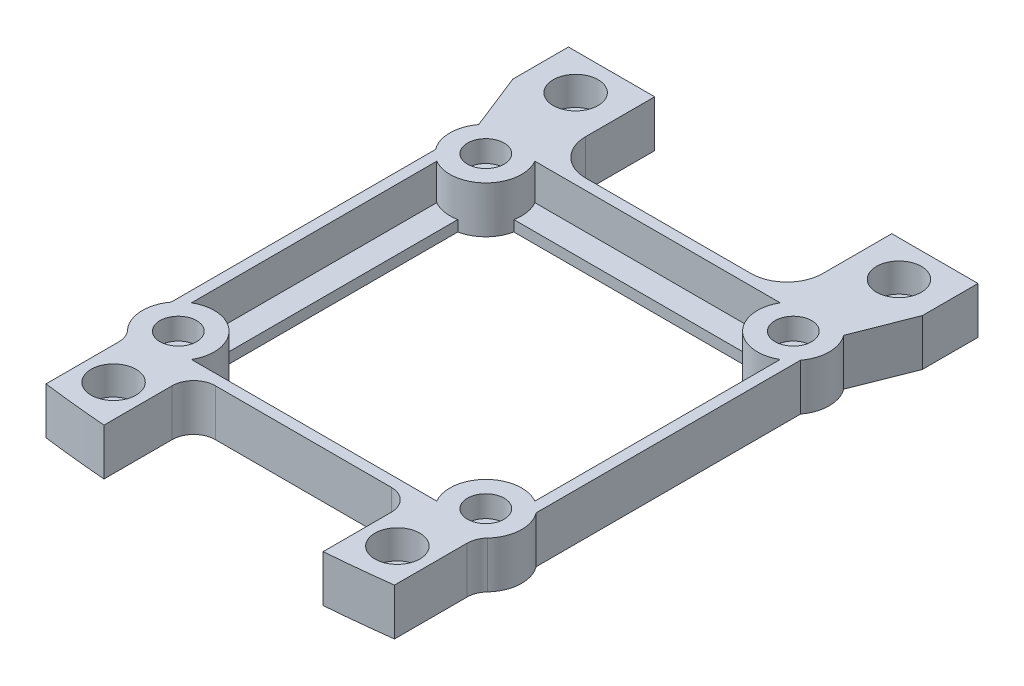
SolidWorks part; units mm, degrees
ref_plane "Front Plane" through (0, 0, 0) normal (0, 0, 1) x (1, 0, 0)
ref_plane "Top Plane" through (0, 0, 0) normal (0, 1, 0) x (1, 0, 0)
ref_plane "Right Plane" through (0, 0, 0) normal (1, 0, 0) x (0, 0, -1)
sketch "Sketch1" plane through (0, 0, 0) normal (0, 1, 0) x (1, 0, 0)
  line L0 (20.4, 20.4) -> (-20.4, 20.4)
  line L1 (21.4, -21.4) -> (-21.4, -21.4) construction
  line L2 (21.4, -21.4) -> (21.4, 21.4) construction
  line L3 (21.4, 21.4) -> (-21.4, 21.4) construction
  line L4 (-21.4, -21.4) -> (-21.4, 21.4) construction
  line L5 (21.4, -21.4) -> (-21.4, 21.4) construction
  line L6 (21.4, 21.4) -> (-21.4, -21.4) construction
  line L7 (-20.4, -20.4) -> (-20.4, 20.4)
  line L8 (20.4, -20.4) -> (-20.4, -20.4)
  line L9 (20.4, -20.4) -> (20.4, 20.4)
  line L10 (25.4, 25.4) -> (-25.4, 25.4)
  line L11 (-25.4, -25.4) -> (-25.4, 25.4)
  line L12 (25.4, -25.4) -> (-25.4, -25.4)
  line L13 (25.4, -25.4) -> (25.4, 25.4)
  circle A0 centre (-21.4, 21.4) radius 1.375
  circle A1 centre (21.4, 21.4) radius 1.375
  circle A2 centre (21.4, -21.4) radius 1.375
  circle A3 centre (-21.4, -21.4) radius 1.375
  point P0 (0, 0)
  dimension "D2" = 2.75
  dimension "D1" = 42.8
  dimension "D3" = 1
  dimension "D4" = 4
extrude "Boss-Extrude1" add sketch "Sketch1" along normal blind 1.5
sketch "Sketch2" plane through (0, 1.5, 0) normal (0, 1, 0) x (1, 0, 0)
  line L0 (23.9, 23.9) -> (-23.9, 23.9)
  line L1 (-23.9, 23.9) -> (-23.9, -23.9)
  line L2 (-23.9, -23.9) -> (23.9, -23.9)
  line L3 (23.9, -23.9) -> (23.9, 23.9)
  line L4 (25.4, -25.4) -> (25.4, 25.4)
  line L5 (25.4, 25.4) -> (-25.4, 25.4)
  line L6 (-25.4, 25.4) -> (-25.4, -25.4)
  line L7 (-25.4, -25.4) -> (25.4, -25.4)
  line L8 (25.4, -25.4) -> (25.4, 25.4)
  line L9 (25.4, 25.4) -> (-25.4, 25.4)
  line L10 (-25.4, 25.4) -> (-25.4, -25.4)
  line L11 (-25.4, -25.4) -> (25.4, -25.4)
  dimension "D1" = 0
  dimension "D2" = 1.5
extrude "Boss-Extrude2" add sketch "Sketch2" along normal blind 5
fillet "Fillet2" radius 3 8 edges at (23.9, 4, -23.9) (25.4, 3.25, -25.4) (23.9, 4, 23.9) (25.4, 3.25, 25.4) (-23.9, 4, 23.9) (-25.4, 3.25, 25.4) (-25.4, 3.25, -25.4) (-23.9, 4, -23.9)
sketch "Sketch5" plane through (0, 6.5, 0) normal (0, 1, 0) x (1, 0, 0)
  circle A0 centre (-21.4, 21.4) radius 5
  circle A1 centre (21.4, 21.4) radius 5
  circle A2 centre (21.4, -21.4) radius 5
  circle A3 centre (-21.4, -21.4) radius 5
  circle A4 centre (21.4, -21.4) radius 1.375 construction
  circle A5 centre (-21.4, -21.4) radius 1.375 construction
  circle A6 centre (21.4, 21.4) radius 1.375 construction
  circle A7 centre (-21.4, 21.4) radius 1.375 construction
  circle A8 centre (21.4, -21.4) radius 1.375
  circle A9 centre (-21.4, -21.4) radius 1.375
  circle A10 centre (21.4, 21.4) radius 1.375
  circle A11 centre (-21.4, 21.4) radius 1.375
  dimension "D1" = 10
extrude "Boss-Extrude3" add sketch "Sketch5" against normal up to surface (6.5 mm away) up to face at (-21.4, 0, 22.775)
sketch "Sketch6" plane through (0, 6.5, 0) normal (0, 1, 0) x (1, 0, 0)
  circle A0 centre (-21.4, 21.4) radius 2.55
  circle A1 centre (21.4, 21.4) radius 2.55
  circle A2 centre (-21.4, -21.4) radius 2.55
  circle A3 centre (21.4, -21.4) radius 2.55
  dimension "D1" = 5.1
extrude "Cut-Extrude1" cut sketch "Sketch6" against normal blind 3
sketch "Sketch7" plane through (0, 6.5, 0) normal (0, 1, 0) x (1, 0, 0)
  line L0 (16.5, 25.4) -> (16.5, 40)
  line L1 (18.4, 25.4) -> (-18.4, 25.4) construction
  line L2 (16.5, 40) -> (28.5, 40)
  line L5 (18.4, 25.4) -> (16.5, 25.4)
  line L7 (28.5, 40) -> (28.5, 32.25)
  line L8 (28.5, 32.25) -> (25.4, 24.4)
  line L9 (25.4, -18.4) -> (25.4, 18.4) construction
  arc A0 (25.4, 18.4) -> (18.4, 25.4) centre (21.4, 21.4) ccw construction
  arc A1 (25.4, 24.4) -> (18.4, 25.4) centre (21.4, 21.4) ccw
  circle A2 centre (22.5, 35) radius 1.55
  point P7 (22.5, 40)
  dimension "D5" = 5
  dimension "D6" = 3.1
  dimension "D1" = 40
  dimension "D2" = 16.5
  dimension "D3" = 12
  dimension "D4" = 7.75
extrude "Boss-Extrude4" add sketch "Sketch7" against normal up to surface (6.5 mm away) up to face at (0, 0, 0)
sketch "Sketch8" plane through (0, 6.5, 0) normal (0, 1, 0) x (1, 0, 0)
  circle A0 centre (22.5, 35) radius 3.125
  dimension "D1" = 6.25
extrude "Cut-Extrude2" cut sketch "Sketch8" against normal blind 4
mirror "Mirror1" about plane through (0, 0, 0) normal (1, 0, 0) of "Cut-Extrude2", "Boss-Extrude4"
fillet "Fillet3" radius 5 2 edges at (16.5, 3.25, -25.4) (-16.5, 3.25, -25.4)
sketch "Sketch9" plane through (0, 6.5, 0) normal (0, 1, 0) x (1, 0, 0)
  line L0 (-24.25, -25.5082) -> (-24.25, -36.9624)
  line L1 (-15.25, -25.4) -> (-15.25, -37.8934)
  line L2 (-18.4, -25.4) -> (18.4, -25.4) construction
  line L3 (-18.4, -25.4) -> (-15.25, -25.4)
  arc A0 (-25.4, -18.4) -> (-18.4, -25.4) centre (-21.4, -21.4) ccw construction
  arc A3 (-24.25, -25.5082) -> (-18.4, -25.4) centre (-21.4, -21.4) ccw
  arc A5 (-24.25, -36.9624) -> (-15.25, -37.8934) centre (0, 153.5) ccw
  arc A7 (-76.8129, -22.4653) -> (-4.75, -38.4412) centre (0, 153.5) ccw construction
  dimension "D1" = 9
  dimension "D2" = 15.25
extrude "Boss-Extrude5" add sketch "Sketch9" against normal up to surface (6.5 mm away) up to face at (0, 0, -18.1088)
sketch "Sketch10" plane through (0, 6.5, 0) normal (0, 1, 0) x (1, 0, 0)
  line L0 (-24.25, -32.06) -> (-15.25, -32.06) construction
  line L1 (-24.25, -25.5082) -> (-24.25, -36.9624) construction
  line L2 (-15.25, -37.8934) -> (-15.25, -25.4) construction
  line L3 (-15.25, -25.4) -> (18.4, -25.4) construction
  circle A0 centre (-19.75, -32.06) radius 3.125
  circle A2 centre (22.5, 35) radius 3.125 construction
  point P9 (-19.75, -32.06)
  dimension "D1" = 6.66
extrude "Cut-Extrude3" cut sketch "Sketch10" against normal blind 4
sketch "Sketch11" plane through (0, 2.5, 0) normal (0, 1, 0) x (1, 0, 0)
  circle A0 centre (-19.75, -32.06) radius 1.55
  dimension "D1" = 3.1
extrude "Cut-Extrude4" cut sketch "Sketch11" against normal through all
mirror "Mirror2" about plane through (0, 0, 0) normal (1, 0, 0) of "Cut-Extrude4", "Cut-Extrude3", "Boss-Extrude5"
fillet "Fillet4" radius 3 4 edges at (-24.25, 3.25, 25.5082) (24.25, 3.25, 25.5082) (15.25, 3.25, 25.4) (-15.25, 3.25, 25.4)
